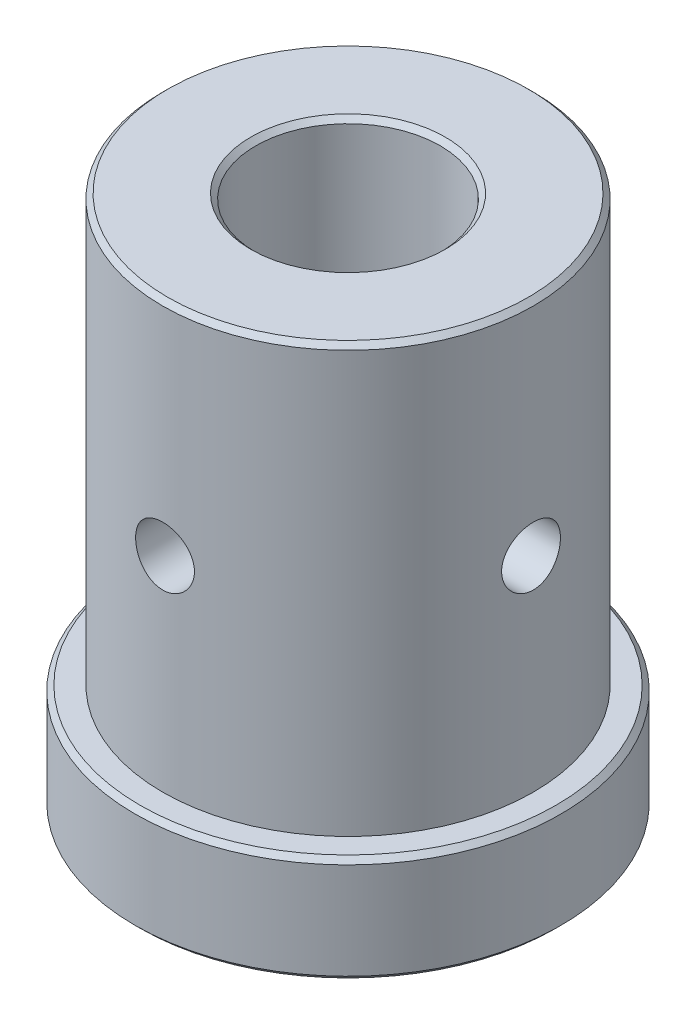
SolidWorks part; units mm, degrees
material "Nylon 101"
ref_plane "Front Plane" through (0, 0, 0) normal (0, 0, 1) x (1, 0, 0)
ref_plane "Top Plane" through (0, 0, 0) normal (0, 1, 0) x (1, 0, 0)
ref_plane "Right Plane" through (0, 0, 0) normal (1, 0, 0) x (0, 0, -1)
sketch "Sketch1" plane through (0, 0, 0) normal (0, 1, 0) x (1, 0, 0)
  circle A0 centre (0, 0) radius 11.049
  dimension "D1" = 22.098
extrude "Boss-Extrude1" add sketch "Sketch1" along normal blind 25.4
sketch "Sketch2" plane through (0, 0, 0) normal (0, -1, 0) x (1, 0, 0)
  circle A0 centre (0, 0) radius 12.7
  dimension "D1" = 25.4
extrude "Boss-Extrude2" add sketch "Sketch2" along normal blind 6.35
sketch "Sketch5" plane through (0, -6.35, 0) normal (0, -1, 0) x (1, 0, 0)
  circle A0 centre (0, 0) radius 11.176
  dimension "D1" = 22.352
extrude "Cut-Extrude2" cut sketch "Sketch5" against normal blind 5.5453
sketch "Sketch6" plane through (0, -0.8047, 0) normal (0, -1, 0) x (1, 0, 0)
  circle A0 centre (0, 0) radius 7.2746
  dimension "D1" = 14.5491
extrude "Cut-Extrude3" cut sketch "Sketch6" against normal blind 0.2
ref_plane "Plane2" through (0, 9.525, 0) normal (0, -1, 0) x (-1, 0, 0)
sketch "Sketch3" plane through (0, -6.35, 0) normal (0, -1, 0) x (1, 0, 0)
  circle A0 centre (0, 0) radius 5.5
  dimension "D1" = 11
extrude "Cut-Extrude1" cut sketch "Sketch3" against normal through all
sketch "Sketch4" plane through (0, -6.35, 0) normal (0, -1, 0) x (1, 0, 0)
  circle A0 centre (0, 0) radius 11.1125
  dimension "D1" = 22.225
chamfer "Chamfer1" distance 0.3 angle 45 6 edges at (0, 0, -12.7) (0, -6.35, -12.7) (0, 25.4, 11.049) (0, 25.4, -5.5) (0, -0.6047, -5.5) (0, -6.35, -11.176)
sketch "Sketch7" plane through (0, 0, 0) normal (0, 0, 1) x (1, 0, 0)
  line L0 (12.4, 0) -> (-12.4, 0) construction
  circle A0 centre (0, 12.192) radius 1.7526
  dimension "D1" = 3.5052
  dimension "D2" = 12.192
extrude "Cut-Extrude4" cut sketch "Sketch7" against normal through all both and the other way through all
sketch "Sketch8" plane through (0, 0, 0) normal (1, 0, 0) x (0, 0, -1)
  line L0 (12.4, 0) -> (-12.4, 0) construction
  circle A0 centre (0, 12.192) radius 1.7526
  dimension "D1" = 3.5052
  dimension "D2" = 12.192
extrude "Cut-Extrude5" cut sketch "Sketch8" against normal through all both and the other way through all
equation "\"D1@Chamfer1\"=.3mm"
